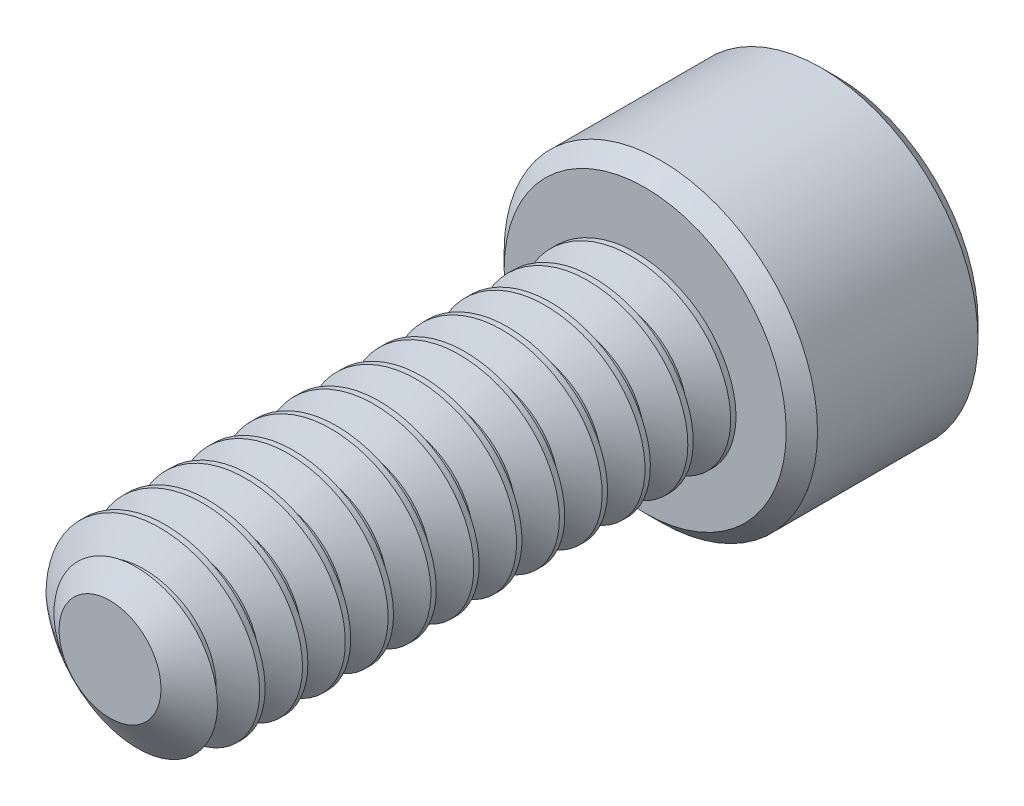
SolidWorks part; units mm, degrees
other "DetailItem1"
ref_plane "Front Plane" through (0, 0, 0) normal (0, 0, 1) x (1, 0, 0)
ref_plane "Top Plane" through (0, 0, 0) normal (0, 1, 0) x (1, 0, 0)
ref_plane "Right Plane" through (0, 0, 0) normal (1, 0, 0) x (0, 0, -1)
sketch "Sketch1" plane through (0, 0, 0) normal (0, 0, 1) x (1, 0, 0)
  circle A0 centre (0, 0) radius 1.4224
  dimension "OD" = 2.8448
extrude "Extrude1" add sketch "Sketch1" against normal blind 7.9375
sketch "Sketch2" plane through (0, 0, 0) normal (0, 0, 1) x (1, 0, 0)
  circle A0 centre (0, 0) radius 1.4224 construction
  circle A1 centre (0, 0) radius 1.4224
curve "Helix/Spiral1" pitch 0.635 height 8.5725 radius 1.4224 centre (0, 0, 0) axis (0, 0, -1) start towards (0, 1, 0) parameters "pitch"=0.635
sketch "Sketch3" plane through (0, 0, 0) normal (1, 0, 0) x (0, 0, -1)
  line L0 (-0.5556, 1.4224) -> (-0.3175, 1.01)
  line L1 (-0.3175, 1.01) -> (-0.2381, 1.01)
  line L2 (-0.2381, 1.01) -> (0, 1.4224)
  line L3 (-0.5556, 1.4224) -> (0, 1.4224)
  line L4 (-0.2778, 1.4224) -> (-0.2778, 1.01) construction
  line L5 (-0.4366, 1.2162) -> (-0.1191, 1.2162) construction
  line L6 (0, 1.4224) -> (0, -1.4224) construction
  dimension "D1" = 0.0794
  dimension "D2" = 0.3175
  dimension "D3" = 60
sweep "Cut-Sweep1" cut profiles "Sketch3" path "Helix/Spiral1" align with end faces yes
sketch "Sketch4" plane through (0, 0, 0) normal (1, 0, 0) x (0, 0, -1)
  line L0 (0.4666, 1.4224) -> (0, 0.756)
  line L1 (0, 0.756) -> (0, 1.4224)
  line L2 (0.4666, 1.4224) -> (0, 1.4224)
  line L3 (-0.5556, 1.4224) -> (0, 1.4224) construction
  line L4 (0, 0) -> (7.0209, 0) construction
  dimension "D1" = 55
  dimension "D2" = 0.254
revolve "Cut-Revolve1" cut sketch "Sketch4" angle 360 about L4
sketch "Sketch5" plane through (0, 0, 0) normal (1, 0, 0) x (0, 0, -1)
  line L0 (7.9375, -1.0149) -> (7.9375, 1.0232) construction
  line L1 (7.9375, 1.5494) -> (0.1202, 1.5494)
  line L2 (7.9375, 1.5494) -> (7.9375, 0)
  line L3 (7.9375, 0) -> (0, 0)
  line L4 (0, 1.2192) -> (0, 0)
  line L5 (0.1202, 1.5494) -> (0, 1.2192)
  line L6 (0, 0) -> (9.9695, 0) construction
  point P3 (0, 1.5494)
  point P10 (0, 1.5494)
  dimension "D1" = 0.3302
  dimension "D2" = 0.127
  dimension "D3" = 20
  dimension "Min Thread" = 0
revolve "partially thread" [suppressed] add sketch "Sketch5" angle 360 about L6
sketch "Sketch6" plane through (0, 0, -7.9375) normal (0, 0, -1) x (-1, 0, 0)
  circle A0 centre (0, 0) radius 2.3241
  dimension "head dia" = 4.6482
extrude "Extrude2" add sketch "Sketch6" along normal blind 2.8448
sketch "Sketch7" plane through (0, 0, -10.7823) normal (0, 0, -1) x (-1, 0, 0)
  line L1 (0, 1.3748) -> (-1.1906, 0.6874)
  line L2 (-1.1906, 0.6874) -> (-1.1906, -0.6874)
  line L3 (-1.1906, -0.6874) -> (0, -1.3748)
  line L4 (0, -1.3748) -> (1.1906, -0.6874)
  line L5 (1.1906, -0.6874) -> (1.1906, 0.6874)
  line L6 (1.1906, 0.6874) -> (0, 1.3748)
  circle A0 centre (0, 0) radius 1.1906 construction
  dimension "hex dia" = 2.3813
extrude "Cut-Extrude1" cut sketch "Sketch7" against normal blind 1.7859
sketch "Sketch8" plane through (0, 0, -10.7823) normal (0, 0, -1) x (-1, 0, 0)
  circle A0 centre (0, 0) radius 1.3748
extrude "Cut-Extrude2" cut sketch "Sketch8" against normal through all draft 45
chamfer "Chamfer1" distance 0.2324 angle 45 2 edges at (-2.3241, 0, -10.7823) (-2.3241, 0, -7.9375)
sketch "Sketch9" plane through (0, 0, 0) normal (1, 0, 0) x (0, 0, -1)
  line L0 (0, 1.4224) -> (0, -1.4224) construction
  line L1 (1.5875, 1.4224) -> (1.5875, -1.4224) construction
  dimension "D1" = 1.5875
equation "\"D3@Helix/Spiral1\" = \"screw length@Extrude1\"+\"pitch@Helix/Spiral1\""
equation "\"D1@Sketch3\" = \"pitch@Helix/Spiral1\"*.125"
equation "\"D2@Sketch3\" = \"pitch@Helix/Spiral1\"*.5"
equation "\"D1@Cut-Extrude1\" = \"hex dia@Sketch7\"*.75"
equation "\"D1@Chamfer1\" = \"head dia@Sketch6\"*.05"
equation "\"D1@Sketch9\" = \"pitch@Helix/Spiral1\"*2.5"
